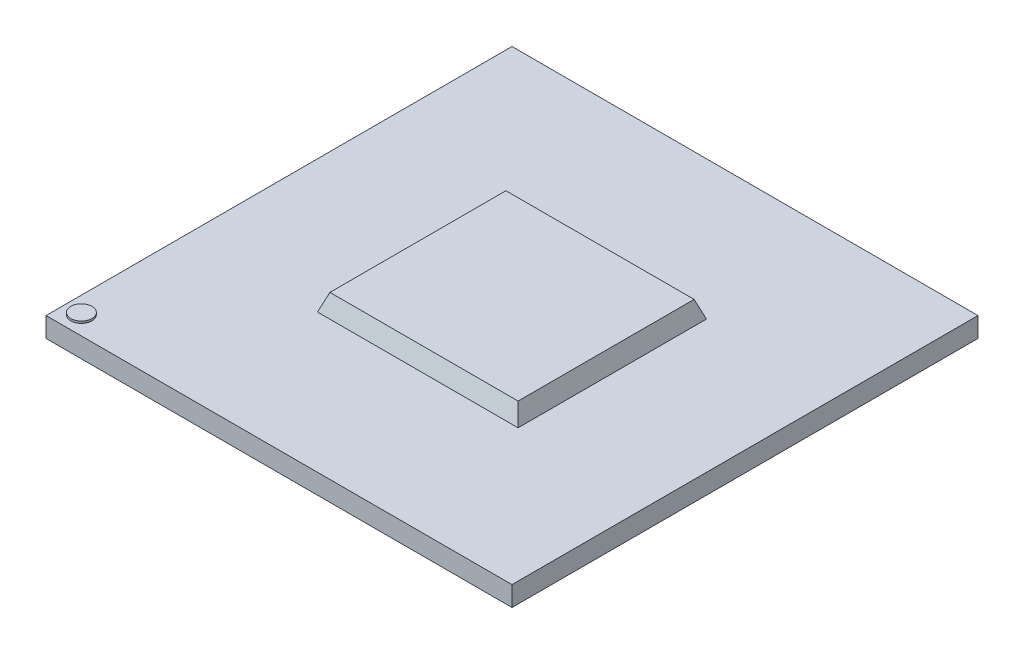
SolidWorks part; units mm, degrees
ref_plane "Front Plane" through (0, 0, 0) normal (0, 0, 1) x (1, 0, 0)
ref_plane "Top Plane" through (0, 0, 0) normal (0, 1, 0) x (1, 0, 0)
ref_plane "Right Plane" through (0, 0, 0) normal (1, 0, 0) x (0, 0, -1)
sketch "Sketch8" plane through (0, 0, 0) normal (0, 1, 0) x (1, 0, 0)
  line L1 (-11.5, 11.5) -> (11.5, 11.5)
  line L2 (-11.5, 11.5) -> (-11.5, -11.5)
  line L3 (-11.5, -11.5) -> (11.5, -11.5)
  line L4 (11.5, 11.5) -> (11.5, -11.5)
extrude "Boss-Extrude4" add sketch "Sketch8" along normal blind 0.98 separate body
sketch "Sketch16" plane through (0, 0.98, 0) normal (0, 1, 0) x (1, 0, 0)
  line L1 (-4.95, 4.65) -> (4.95, 4.65)
  line L2 (-4.95, 4.65) -> (-4.95, -4.65)
  line L3 (-4.95, -4.65) -> (4.95, -4.65)
  line L4 (4.95, 4.65) -> (4.95, -4.65)
extrude "Boss-Extrude11" add sketch "Sketch16" along normal blind 0.84 draft 20
ref_plane "Plane1" through (0, 0, 0) normal (-0.7071, 0, 0.7071) x (0.7071, 0, 0.7071)
ref_plane "Plane2" through (0, 0, 0) normal (0.7071, 0, 0.7071) x (0.7071, 0, -0.7071)
ref_axis "Axis1" through (0, -1.6461, 0) along (0, 1, 0)
sketch "Sketch17" plane through (0, 0.98, 0) normal (0, 1, 0) x (1, 0, 0)
  circle A0 centre (-10.6592, -10.5939) radius 0.5221
extrude "Boss-Extrude12" add sketch "Sketch17" along normal blind 0.1 contours A0
